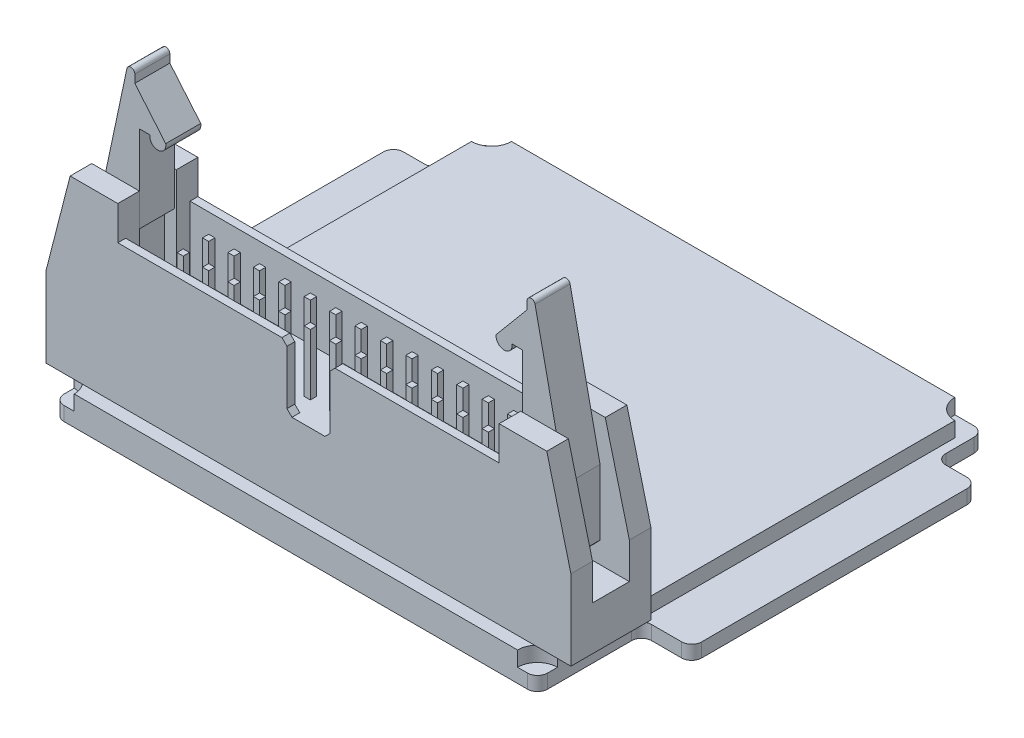
SolidWorks part; units mm, degrees
ref_plane "Front Plane" through (0, 0, 0) normal (0, 0, 1) x (1, 0, 0)
ref_plane "Top Plane" through (0, 0, 0) normal (0, 1, 0) x (1, 0, 0)
ref_plane "Right Plane" through (0, 0, 0) normal (1, 0, 0) x (0, 0, -1)
ref_plane "Plane1" through (0, 0, 0) normal (0, 0, 1) x (1, 0, 0)
sketch "Sketch1" plane through (0, 0, 0) normal (0, 0, 1) x (1, 0, 0)
  line L0 (-26.225, 8) -> (-26.225, 0)
  line L1 (-26.225, 0) -> (26.225, 0)
  line L2 (26.225, 0) -> (26.225, 8)
  line L3 (26.225, 8) -> (23.815, 17.4)
  line L4 (23.815, 17.4) -> (19.05, 17.4)
  line L5 (19.05, 17.4) -> (19.05, 14)
  line L6 (19.05, 14) -> (-19.05, 14)
  line L7 (-19.05, 14) -> (-19.05, 17.4)
  line L8 (-19.05, 17.4) -> (-23.815, 17.4)
  line L9 (-23.815, 17.4) -> (-26.225, 8)
extrude "Boss-Extrude1" add sketch "Sketch1" against normal blind 4 and the other way blind 4
ref_plane "Plane2" through (0, 14, 0) normal (0, 1, 0) x (1, 0, 0)
sketch "Sketch2" plane through (0, 14, 0) normal (0, 1, 0) x (1, 0, 0)
  line L0 (-19.05, 3.215) -> (-19.05, -3.215)
  line L1 (-19.05, -3.215) -> (19.05, -3.215)
  line L2 (19.05, -3.215) -> (19.05, 3.215)
  line L3 (19.05, 3.215) -> (-19.05, 3.215)
extrude "Cut-Extrude1" cut sketch "Sketch2" against normal blind 6.4
ref_plane "Plane3" through (0, 0, 4.075) normal (0, 0, 1) x (1, 0, 0)
sketch "Sketch3" plane through (0, 0, 4.075) normal (0, 0, 1) x (1, 0, 0)
  line L0 (-2.65, 14) -> (-2.15, 13.5)
  line L1 (-2.15, 13.5) -> (-2.15, 8.1)
  line L2 (-2.15, 8.1) -> (-1.65, 7.6)
  line L3 (-1.65, 7.6) -> (1.65, 7.6)
  line L4 (1.65, 7.6) -> (2.15, 8.1)
  line L5 (2.15, 8.1) -> (2.15, 13.5)
  line L6 (2.15, 13.5) -> (2.65, 14)
  line L7 (2.65, 14) -> (-2.65, 14)
extrude "Cut-Extrude2" cut sketch "Sketch3" against normal blind 1.5
ref_plane "Plane4" through (26.225, 0, 0) normal (1, 0, 0) x (0, 0, -1)
sketch "Sketch4" plane through (26.225, 0, 0) normal (1, 0, 0) x (0, 0, -1)
  line L0 (-1.84, 4.4) -> (1.84, 4.4)
  line L1 (1.84, 4.4) -> (1.84, 17.4)
  line L2 (1.84, 17.4) -> (-1.84, 17.4)
  line L3 (-1.84, 17.4) -> (-1.84, 4.4)
extrude "Cut-Extrude3" cut sketch "Sketch4" against normal blind 7.2 and the other way blind 7.2
ref_plane "Plane5" through (-26.225, 0, 0) normal (1, 0, 0) x (0, 0, -1)
sketch "Sketch5" plane through (-26.225, 0, 0) normal (1, 0, 0) x (0, 0, -1)
  line L0 (-1.84, 4.4) -> (1.84, 4.4)
  line L1 (1.84, 4.4) -> (1.84, 17.4)
  line L2 (1.84, 17.4) -> (-1.84, 17.4)
  line L3 (-1.84, 17.4) -> (-1.84, 4.4)
extrude "Cut-Extrude4" cut sketch "Sketch5" against normal blind 7.2 and the other way blind 7.2
ref_plane "Plane6" through (0, 0, 0) normal (0, 0, 1) x (1, 0, 0)
sketch "Sketch6" plane through (0, 0, 0) normal (0, 0, 1) x (1, 0, 0)
  circle A0 centre (22.225, 9.86) radius 0.5
extrude "Boss-Extrude2" add sketch "Sketch6" against normal blind 3.8 and the other way blind 3.8
ref_plane "Plane7" through (0, 0, 0) normal (0, 0, 1) x (1, 0, 0)
sketch "Sketch7" plane through (0, 0, 0) normal (0, 0, 1) x (1, 0, 0)
  line L0 (18.1002, 22.6945) -> (19.155, 22.6945)
  line L1 (19.155, 22.6945) -> (19.155, 14.023)
  line L2 (19.155, 14.023) -> (20.155, 14.023)
  line L3 (20.155, 14.023) -> (20.155, 6.6203)
  line L4 (23.385, 6.6203) -> (23.385, 13.1622)
  line L5 (23.385, 13.1622) -> (20.3913, 27.283)
  line L6 (19.6, 27.2) -> (19.6, 26.4)
  line L7 (19.6, 26.4) -> (16.5146, 22.723)
  arc A0 (16.5146, 22.723) -> (18.1002, 22.6945) centre (17.305, 22.5759) ccw
  arc A1 (20.155, 6.6203) -> (23.385, 6.6203) centre (21.77, 7.8) ccw
  arc A2 (20.3913, 27.283) -> (19.6, 27.2) centre (20, 27.2) ccw
extrude "Boss-Extrude3" add sketch "Sketch7" against normal blind 1.75 and the other way blind 1.75
ref_plane "Plane8" through (0, 0, 0) normal (0, 0, 1) x (1, 0, 0)
sketch "Sketch8" plane through (0, 0, 0) normal (0, 0, 1) x (1, 0, 0)
  circle A0 centre (-22.225, 9.86) radius 0.5
extrude "Boss-Extrude4" add sketch "Sketch8" against normal blind 1.9 and the other way blind 1.9
ref_plane "Plane9" through (0, 0, 0) normal (0, 0, 1) x (1, 0, 0)
sketch "Sketch9" plane through (0, 0, 0) normal (0, 0, 1) x (1, 0, 0)
  line L0 (-23.385, 13.1622) -> (-23.385, 6.6203)
  line L1 (-20.155, 6.6203) -> (-20.155, 14.023)
  line L2 (-20.155, 14.023) -> (-19.155, 14.023)
  line L3 (-19.155, 14.023) -> (-19.155, 22.6945)
  line L4 (-19.155, 22.6945) -> (-18.1002, 22.6945)
  line L5 (-16.5146, 22.723) -> (-19.6, 26.4)
  line L6 (-19.6, 26.4) -> (-19.6, 27.2)
  line L7 (-20.3913, 27.283) -> (-23.385, 13.1622)
  arc A0 (-23.385, 6.6203) -> (-20.155, 6.6203) centre (-21.77, 7.8) ccw
  arc A1 (-18.1002, 22.6945) -> (-16.5146, 22.723) centre (-17.305, 22.5759) ccw
  arc A2 (-19.6, 27.2) -> (-20.3913, 27.283) centre (-20, 27.2) ccw
extrude "Boss-Extrude5" add sketch "Sketch9" against normal blind 1.75 and the other way blind 1.75
ref_plane "Plane10" through (0, 7.6, 0) normal (0, 1, 0) x (1, 0, 0)
sketch "Sketch10" plane through (0, 7.6, 0) normal (0, 1, 0) x (1, 0, 0)
  line L0 (-15.55, -0.96) -> (-15.55, -1.58)
  line L1 (-15.55, -1.58) -> (-14.93, -1.58)
  line L2 (-14.93, -1.58) -> (-14.93, -0.96)
  line L3 (-14.93, -0.96) -> (-15.55, -0.96)
extrude "Boss-Extrude6" add sketch "Sketch10" along normal blind 6.1
ref_plane "Plane11" through (0, 7.6, 0) normal (0, 1, 0) x (1, 0, 0)
sketch "Sketch11" plane through (0, 7.6, 0) normal (0, 1, 0) x (1, 0, 0)
  line L0 (-13.01, -0.96) -> (-13.01, -1.58)
  line L1 (-13.01, -1.58) -> (-12.39, -1.58)
  line L2 (-12.39, -1.58) -> (-12.39, -0.96)
  line L3 (-12.39, -0.96) -> (-13.01, -0.96)
extrude "Boss-Extrude7" add sketch "Sketch11" along normal blind 6.1
ref_plane "Plane12" through (0, 7.6, 0) normal (0, 1, 0) x (1, 0, 0)
sketch "Sketch12" plane through (0, 7.6, 0) normal (0, 1, 0) x (1, 0, 0)
  line L0 (-10.47, -0.96) -> (-10.47, -1.58)
  line L1 (-10.47, -1.58) -> (-9.85, -1.58)
  line L2 (-9.85, -1.58) -> (-9.85, -0.96)
  line L3 (-9.85, -0.96) -> (-10.47, -0.96)
extrude "Boss-Extrude8" add sketch "Sketch12" along normal blind 6.1
ref_plane "Plane13" through (0, 7.6, 0) normal (0, 1, 0) x (1, 0, 0)
sketch "Sketch13" plane through (0, 7.6, 0) normal (0, 1, 0) x (1, 0, 0)
  line L0 (-7.93, -0.96) -> (-7.93, -1.58)
  line L1 (-7.93, -1.58) -> (-7.31, -1.58)
  line L2 (-7.31, -1.58) -> (-7.31, -0.96)
  line L3 (-7.31, -0.96) -> (-7.93, -0.96)
extrude "Boss-Extrude9" add sketch "Sketch13" along normal blind 6.1
ref_plane "Plane14" through (0, 7.6, 0) normal (0, 1, 0) x (1, 0, 0)
sketch "Sketch14" plane through (0, 7.6, 0) normal (0, 1, 0) x (1, 0, 0)
  line L0 (-5.39, -0.96) -> (-5.39, -1.58)
  line L1 (-5.39, -1.58) -> (-4.77, -1.58)
  line L2 (-4.77, -1.58) -> (-4.77, -0.96)
  line L3 (-4.77, -0.96) -> (-5.39, -0.96)
extrude "Boss-Extrude10" add sketch "Sketch14" along normal blind 6.1
ref_plane "Plane15" through (0, 7.6, 0) normal (0, 1, 0) x (1, 0, 0)
sketch "Sketch15" plane through (0, 7.6, 0) normal (0, 1, 0) x (1, 0, 0)
  line L0 (-2.85, -0.96) -> (-2.85, -1.58)
  line L1 (-2.85, -1.58) -> (-2.23, -1.58)
  line L2 (-2.23, -1.58) -> (-2.23, -0.96)
  line L3 (-2.23, -0.96) -> (-2.85, -0.96)
extrude "Boss-Extrude11" add sketch "Sketch15" along normal blind 6.1
ref_plane "Plane16" through (0, 7.6, 0) normal (0, 1, 0) x (1, 0, 0)
sketch "Sketch16" plane through (0, 7.6, 0) normal (0, 1, 0) x (1, 0, 0)
  line L0 (-0.31, -0.96) -> (-0.31, -1.58)
  line L1 (-0.31, -1.58) -> (0.31, -1.58)
  line L2 (0.31, -1.58) -> (0.31, -0.96)
  line L3 (0.31, -0.96) -> (-0.31, -0.96)
extrude "Boss-Extrude12" add sketch "Sketch16" along normal blind 6.1
ref_plane "Plane17" through (0, 7.6, 0) normal (0, 1, 0) x (1, 0, 0)
sketch "Sketch17" plane through (0, 7.6, 0) normal (0, 1, 0) x (1, 0, 0)
  line L0 (2.23, -0.96) -> (2.23, -1.58)
  line L1 (2.23, -1.58) -> (2.85, -1.58)
  line L2 (2.85, -1.58) -> (2.85, -0.96)
  line L3 (2.85, -0.96) -> (2.23, -0.96)
extrude "Boss-Extrude13" add sketch "Sketch17" along normal blind 6.1
ref_plane "Plane18" through (0, 7.6, 0) normal (0, 1, 0) x (1, 0, 0)
sketch "Sketch18" plane through (0, 7.6, 0) normal (0, 1, 0) x (1, 0, 0)
  line L0 (4.77, -0.96) -> (4.77, -1.58)
  line L1 (4.77, -1.58) -> (5.39, -1.58)
  line L2 (5.39, -1.58) -> (5.39, -0.96)
  line L3 (5.39, -0.96) -> (4.77, -0.96)
extrude "Boss-Extrude14" add sketch "Sketch18" along normal blind 6.1
ref_plane "Plane19" through (0, 7.6, 0) normal (0, 1, 0) x (1, 0, 0)
sketch "Sketch19" plane through (0, 7.6, 0) normal (0, 1, 0) x (1, 0, 0)
  line L0 (7.31, -0.96) -> (7.31, -1.58)
  line L1 (7.31, -1.58) -> (7.93, -1.58)
  line L2 (7.93, -1.58) -> (7.93, -0.96)
  line L3 (7.93, -0.96) -> (7.31, -0.96)
extrude "Boss-Extrude15" add sketch "Sketch19" along normal blind 6.1
ref_plane "Plane20" through (0, 7.6, 0) normal (0, 1, 0) x (1, 0, 0)
sketch "Sketch20" plane through (0, 7.6, 0) normal (0, 1, 0) x (1, 0, 0)
  line L0 (9.85, -0.96) -> (9.85, -1.58)
  line L1 (9.85, -1.58) -> (10.47, -1.58)
  line L2 (10.47, -1.58) -> (10.47, -0.96)
  line L3 (10.47, -0.96) -> (9.85, -0.96)
extrude "Boss-Extrude16" add sketch "Sketch20" along normal blind 6.1
ref_plane "Plane21" through (0, 7.6, 0) normal (0, 1, 0) x (1, 0, 0)
sketch "Sketch21" plane through (0, 7.6, 0) normal (0, 1, 0) x (1, 0, 0)
  line L0 (12.39, -0.96) -> (12.39, -1.58)
  line L1 (12.39, -1.58) -> (13.01, -1.58)
  line L2 (13.01, -1.58) -> (13.01, -0.96)
  line L3 (13.01, -0.96) -> (12.39, -0.96)
extrude "Boss-Extrude17" add sketch "Sketch21" along normal blind 6.1
ref_plane "Plane22" through (0, 7.6, 0) normal (0, 1, 0) x (1, 0, 0)
sketch "Sketch22" plane through (0, 7.6, 0) normal (0, 1, 0) x (1, 0, 0)
  line L0 (14.93, -0.96) -> (14.93, -1.58)
  line L1 (14.93, -1.58) -> (15.55, -1.58)
  line L2 (15.55, -1.58) -> (15.55, -0.96)
  line L3 (15.55, -0.96) -> (14.93, -0.96)
extrude "Boss-Extrude18" add sketch "Sketch22" along normal blind 6.1
ref_plane "Plane23" through (0, 7.6, 0) normal (0, 1, 0) x (1, 0, 0)
sketch "Sketch23" plane through (0, 7.6, 0) normal (0, 1, 0) x (1, 0, 0)
  line L0 (-15.55, 1.58) -> (-15.55, 0.96)
  line L1 (-15.55, 0.96) -> (-14.93, 0.96)
  line L2 (-14.93, 0.96) -> (-14.93, 1.58)
  line L3 (-14.93, 1.58) -> (-15.55, 1.58)
extrude "Boss-Extrude19" add sketch "Sketch23" along normal blind 6.1
ref_plane "Plane24" through (0, 7.6, 0) normal (0, 1, 0) x (1, 0, 0)
sketch "Sketch24" plane through (0, 7.6, 0) normal (0, 1, 0) x (1, 0, 0)
  line L0 (-13.01, 1.58) -> (-13.01, 0.96)
  line L1 (-13.01, 0.96) -> (-12.39, 0.96)
  line L2 (-12.39, 0.96) -> (-12.39, 1.58)
  line L3 (-12.39, 1.58) -> (-13.01, 1.58)
extrude "Boss-Extrude20" add sketch "Sketch24" along normal blind 6.1
ref_plane "Plane25" through (0, 7.6, 0) normal (0, 1, 0) x (1, 0, 0)
sketch "Sketch25" plane through (0, 7.6, 0) normal (0, 1, 0) x (1, 0, 0)
  line L0 (-10.47, 1.58) -> (-10.47, 0.96)
  line L1 (-10.47, 0.96) -> (-9.85, 0.96)
  line L2 (-9.85, 0.96) -> (-9.85, 1.58)
  line L3 (-9.85, 1.58) -> (-10.47, 1.58)
extrude "Boss-Extrude21" add sketch "Sketch25" along normal blind 6.1
ref_plane "Plane26" through (0, 7.6, 0) normal (0, 1, 0) x (1, 0, 0)
sketch "Sketch26" plane through (0, 7.6, 0) normal (0, 1, 0) x (1, 0, 0)
  line L0 (-7.93, 1.58) -> (-7.93, 0.96)
  line L1 (-7.93, 0.96) -> (-7.31, 0.96)
  line L2 (-7.31, 0.96) -> (-7.31, 1.58)
  line L3 (-7.31, 1.58) -> (-7.93, 1.58)
extrude "Boss-Extrude22" add sketch "Sketch26" along normal blind 6.1
ref_plane "Plane27" through (0, 7.6, 0) normal (0, 1, 0) x (1, 0, 0)
sketch "Sketch27" plane through (0, 7.6, 0) normal (0, 1, 0) x (1, 0, 0)
  line L0 (-5.39, 1.58) -> (-5.39, 0.96)
  line L1 (-5.39, 0.96) -> (-4.77, 0.96)
  line L2 (-4.77, 0.96) -> (-4.77, 1.58)
  line L3 (-4.77, 1.58) -> (-5.39, 1.58)
extrude "Boss-Extrude23" add sketch "Sketch27" along normal blind 6.1
ref_plane "Plane28" through (0, 7.6, 0) normal (0, 1, 0) x (1, 0, 0)
sketch "Sketch28" plane through (0, 7.6, 0) normal (0, 1, 0) x (1, 0, 0)
  line L0 (-2.85, 1.58) -> (-2.85, 0.96)
  line L1 (-2.85, 0.96) -> (-2.23, 0.96)
  line L2 (-2.23, 0.96) -> (-2.23, 1.58)
  line L3 (-2.23, 1.58) -> (-2.85, 1.58)
extrude "Boss-Extrude24" add sketch "Sketch28" along normal blind 6.1
ref_plane "Plane29" through (0, 7.6, 0) normal (0, 1, 0) x (1, 0, 0)
sketch "Sketch29" plane through (0, 7.6, 0) normal (0, 1, 0) x (1, 0, 0)
  line L0 (-0.31, 1.58) -> (-0.31, 0.96)
  line L1 (-0.31, 0.96) -> (0.31, 0.96)
  line L2 (0.31, 0.96) -> (0.31, 1.58)
  line L3 (0.31, 1.58) -> (-0.31, 1.58)
extrude "Boss-Extrude25" add sketch "Sketch29" along normal blind 6.1
ref_plane "Plane30" through (0, 7.6, 0) normal (0, 1, 0) x (1, 0, 0)
sketch "Sketch30" plane through (0, 7.6, 0) normal (0, 1, 0) x (1, 0, 0)
  line L0 (2.23, 1.58) -> (2.23, 0.96)
  line L1 (2.23, 0.96) -> (2.85, 0.96)
  line L2 (2.85, 0.96) -> (2.85, 1.58)
  line L3 (2.85, 1.58) -> (2.23, 1.58)
extrude "Boss-Extrude26" add sketch "Sketch30" along normal blind 6.1
ref_plane "Plane31" through (0, 7.6, 0) normal (0, 1, 0) x (1, 0, 0)
sketch "Sketch31" plane through (0, 7.6, 0) normal (0, 1, 0) x (1, 0, 0)
  line L0 (4.77, 1.58) -> (4.77, 0.96)
  line L1 (4.77, 0.96) -> (5.39, 0.96)
  line L2 (5.39, 0.96) -> (5.39, 1.58)
  line L3 (5.39, 1.58) -> (4.77, 1.58)
extrude "Boss-Extrude27" add sketch "Sketch31" along normal blind 6.1
ref_plane "Plane32" through (0, 7.6, 0) normal (0, 1, 0) x (1, 0, 0)
sketch "Sketch32" plane through (0, 7.6, 0) normal (0, 1, 0) x (1, 0, 0)
  line L0 (7.31, 1.58) -> (7.31, 0.96)
  line L1 (7.31, 0.96) -> (7.93, 0.96)
  line L2 (7.93, 0.96) -> (7.93, 1.58)
  line L3 (7.93, 1.58) -> (7.31, 1.58)
extrude "Boss-Extrude28" add sketch "Sketch32" along normal blind 6.1
ref_plane "Plane33" through (0, 7.6, 0) normal (0, 1, 0) x (1, 0, 0)
sketch "Sketch33" plane through (0, 7.6, 0) normal (0, 1, 0) x (1, 0, 0)
  line L0 (9.85, 1.58) -> (9.85, 0.96)
  line L1 (9.85, 0.96) -> (10.47, 0.96)
  line L2 (10.47, 0.96) -> (10.47, 1.58)
  line L3 (10.47, 1.58) -> (9.85, 1.58)
extrude "Boss-Extrude29" add sketch "Sketch33" along normal blind 6.1
ref_plane "Plane34" through (0, 7.6, 0) normal (0, 1, 0) x (1, 0, 0)
sketch "Sketch34" plane through (0, 7.6, 0) normal (0, 1, 0) x (1, 0, 0)
  line L0 (12.39, 1.58) -> (12.39, 0.96)
  line L1 (12.39, 0.96) -> (13.01, 0.96)
  line L2 (13.01, 0.96) -> (13.01, 1.58)
  line L3 (13.01, 1.58) -> (12.39, 1.58)
extrude "Boss-Extrude30" add sketch "Sketch34" along normal blind 6.1
ref_plane "Plane35" through (0, 7.6, 0) normal (0, 1, 0) x (1, 0, 0)
sketch "Sketch35" plane through (0, 7.6, 0) normal (0, 1, 0) x (1, 0, 0)
  line L0 (14.93, 1.58) -> (14.93, 0.96)
  line L1 (14.93, 0.96) -> (15.55, 0.96)
  line L2 (15.55, 0.96) -> (15.55, 1.58)
  line L3 (15.55, 1.58) -> (14.93, 1.58)
extrude "Boss-Extrude31" add sketch "Sketch35" along normal blind 6.1
ref_plane "Plane36" through (0, 0, 0) normal (0, 1, 0) x (1, 0, 0)
sketch "Sketch36" plane through (0, 0, 0) normal (0, 1, 0) x (1, 0, 0)
  line L0 (-22.15, -5.26) -> (22.15, -5.26)
  line L1 (24.15, -3.26) -> (24.15, 36.44)
  line L2 (22.15, 38.44) -> (-22.15, 38.44)
  line L3 (-24.15, 36.44) -> (-24.15, -3.26)
  arc A0 (-24.15, -3.26) -> (-22.15, -5.26) centre (-24.15, -5.26) cw
  arc A1 (22.15, -5.26) -> (24.15, -3.26) centre (24.15, -5.26) cw
  arc A2 (24.15, 36.44) -> (22.15, 38.44) centre (24.15, 38.44) cw
  arc A3 (-22.15, 38.44) -> (-24.15, 36.44) centre (-24.15, 38.44) cw
extrude "Boss-Extrude32" add sketch "Sketch36" against normal blind 1.5
ref_plane "Plane37" through (0, -1.5, 0) normal (0, 1, 0) x (1, 0, 0)
sketch "Sketch37" plane through (0, -1.5, 0) normal (0, 1, 0) x (1, 0, 0)
  line L0 (-28.15, 5.14) -> (-25.15, 5.14)
  line L1 (-24.15, 4.14) -> (-24.15, -4.26)
  line L2 (-23.15, -5.26) -> (23.15, -5.26)
  line L3 (24.15, -4.26) -> (24.15, 4.14)
  line L4 (25.15, 5.14) -> (28.15, 5.14)
  line L5 (29.15, 6.14) -> (29.15, 32.64)
  line L6 (28.15, 33.64) -> (26.05, 33.64)
  line L7 (25.05, 34.64) -> (25.05, 37.44)
  line L8 (24.05, 38.44) -> (-24.05, 38.44)
  line L9 (-25.05, 37.44) -> (-25.05, 34.64)
  line L10 (-26.05, 33.64) -> (-28.15, 33.64)
  line L11 (-29.15, 32.64) -> (-29.15, 6.14)
  arc A0 (-29.15, 6.14) -> (-28.15, 5.14) centre (-28.15, 6.14) ccw
  arc A1 (-25.15, 5.14) -> (-24.15, 4.14) centre (-25.15, 4.14) cw
  arc A2 (-24.15, -4.26) -> (-23.15, -5.26) centre (-23.15, -4.26) ccw
  arc A3 (23.15, -5.26) -> (24.15, -4.26) centre (23.15, -4.26) ccw
  arc A4 (24.15, 4.14) -> (25.15, 5.14) centre (25.15, 4.14) cw
  arc A5 (28.15, 5.14) -> (29.15, 6.14) centre (28.15, 6.14) ccw
  arc A6 (29.15, 32.64) -> (28.15, 33.64) centre (28.15, 32.64) ccw
  arc A7 (26.05, 33.64) -> (25.05, 34.64) centre (26.05, 34.64) cw
  arc A8 (25.05, 37.44) -> (24.05, 38.44) centre (24.05, 37.44) ccw
  arc A9 (-24.05, 38.44) -> (-25.05, 37.44) centre (-24.05, 37.44) ccw
  arc A10 (-25.05, 34.64) -> (-26.05, 33.64) centre (-26.05, 34.64) cw
  arc A11 (-28.15, 33.64) -> (-29.15, 32.64) centre (-28.15, 32.64) ccw
extrude "Boss-Extrude33" add sketch "Sketch37" against normal blind 1.4
